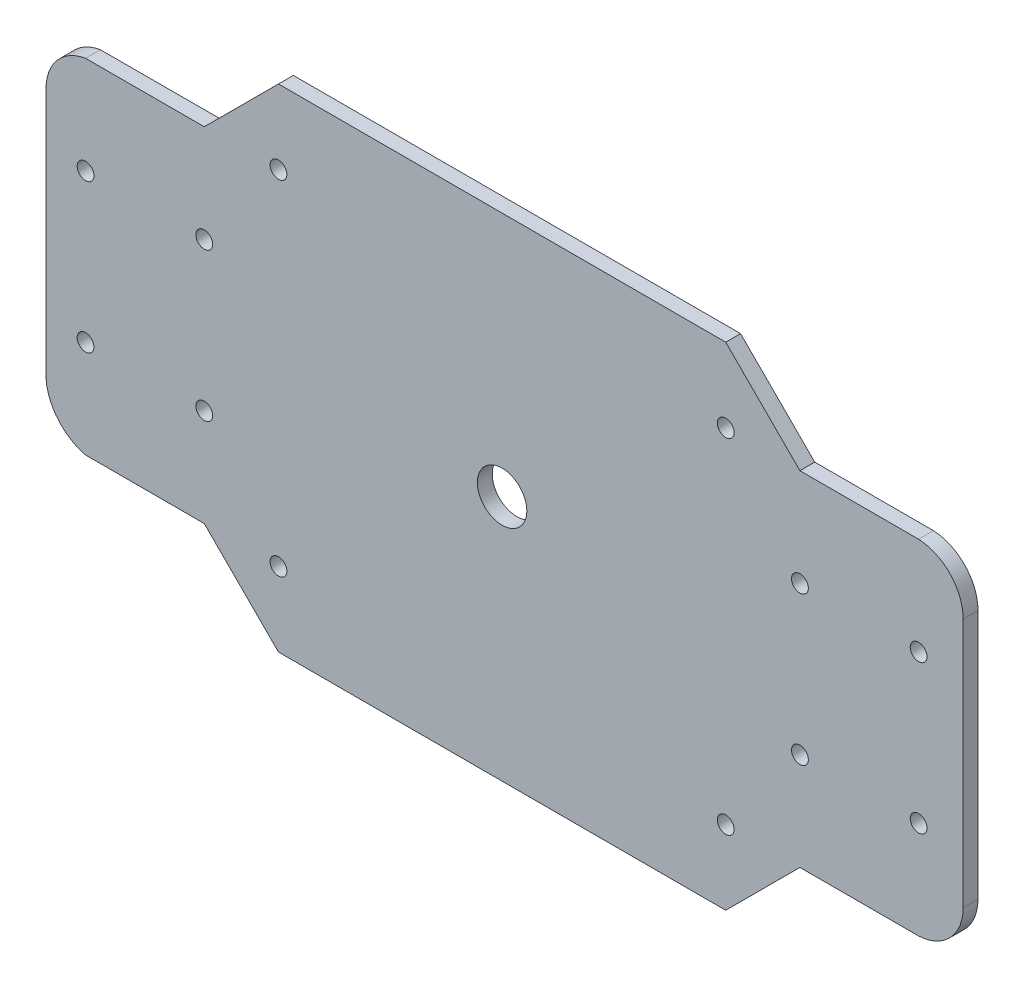
SolidWorks part; units mm, degrees
ref_plane "Front Plane" through (0, 0, 0) normal (0, 0, 1) x (1, 0, 0)
ref_plane "Top Plane" through (0, 0, 0) normal (0, 1, 0) x (1, 0, 0)
ref_plane "Right Plane" through (0, 0, 0) normal (1, 0, 0) x (0, 0, -1)
sketch "Sketch2" plane through (0, 0, 0) normal (0, 0, 1) x (1, 0, 0)
  line L0 (-49.4111, -41.7129) -> (-34.4111, -26.7241)
  line L5 (-73.4111, -41.7353) -> (-49.4111, -41.7129)
  line L7 (-73.4111, -111.1931) -> (-49.4111, -111.1931)
  line L9 (-34.4111, -26.7241) -> (56.0129, -26.7241)
  line L10 (56.0129, -26.7241) -> (71.0129, -41.7241)
  line L11 (-49.4111, -111.1931) -> (-34.4111, -126.1931)
  line L12 (-34.4111, -126.1931) -> (56.0129, -126.1931)
  line L13 (56.0129, -126.1931) -> (71.0129, -111.1931)
  line L14 (71.0129, -41.7241) -> (95.0129, -41.7241)
  line L15 (71.0129, -111.1931) -> (95.0129, -111.1931)
  line L18 (-81.4111, -51.1621) -> (-81.4111, -101.7478)
  line L19 (104.0175, -51.2105) -> (104.0129, -101.7536)
  arc A0 (-73.4111, -41.7353) -> (-81.4111, -51.1621) centre (-71.9614, -51.0735) ccw
  arc A1 (-81.4111, -101.7478) -> (-73.4111, -111.1931) centre (-70.9284, -100.9797) ccw
  arc A2 (104.0175, -51.2105) -> (95.0129, -41.7241) centre (94.5674, -51.1637) ccw
  arc A3 (95.0129, -111.1931) -> (104.0129, -101.7536) centre (94.5627, -101.7536) ccw
  circle A4 centre (-49.4111, -61.4586) radius 1.7
  circle A5 centre (-73.4111, -61.4586) radius 1.7
  circle A6 centre (-73.4111, -91.4586) radius 1.7
  circle A7 centre (-49.4111, -91.4586) radius 1.7
  circle A8 centre (95.0129, -91.4586) radius 1.7
  circle A9 centre (71.0129, -91.4586) radius 1.7
  circle A10 centre (95.0129, -61.4586) radius 1.7
  circle A11 centre (71.0129, -61.4586) radius 1.7
  circle A12 centre (10.8009, -76.383) radius 5
  circle A13 centre (-34.4111, -41.7241) radius 1.7
  circle A14 centre (-34.4111, -111.1931) radius 1.7
  circle A15 centre (56.0129, -111.1931) radius 1.7
  circle A16 centre (56.0129, -41.7241) radius 1.7
  point P46 (83.0129, -41.7241)
  point P47 (-61.4111, -111.1931)
  point P48 (10.8009, -126.1931)
  point P49 (9.2944, -76.383)
  point P50 (0, 0)
  point P51 (-61.4111, -41.7241)
  point P52 (10.8009, -26.7241)
  point P53 (0, 0)
  point P54 (0, 0)
  point P55 (0, 0)
  point P56 (0, 0)
  point P57 (0, 0)
  point P58 (0, 0)
  point P59 (0, 0)
  point P60 (0, 0)
  point P61 (0, 0)
  point P62 (0, 0)
  dimension "D1" = 24
  dimension "D8" = 30
  dimension "D12" = 90.424
  dimension "D15" = 15
  dimension "D16" = 15
  dimension "D22" = 19.7345
  dimension "D2" = 30
  dimension "D3" = 90.424
  dimension "D4" = 24
  dimension "D5" = 30
  dimension "D6" = 24
  dimension "D7" = 24
  dimension "D9" = 30
  dimension "D10" = 69.469
  dimension "D11" = 69.469
  dimension "D13" = 15
  dimension "D14" = 15
  dimension "D17" = 15
  dimension "D18" = 15
  dimension "D19" = 19.7345
  dimension "D20" = 15
  dimension "D21" = 15
  dimension "D23" = 15
  dimension "D24" = 15
extrude "Boss-Extrude4" add sketch "Sketch2" along normal blind 3
